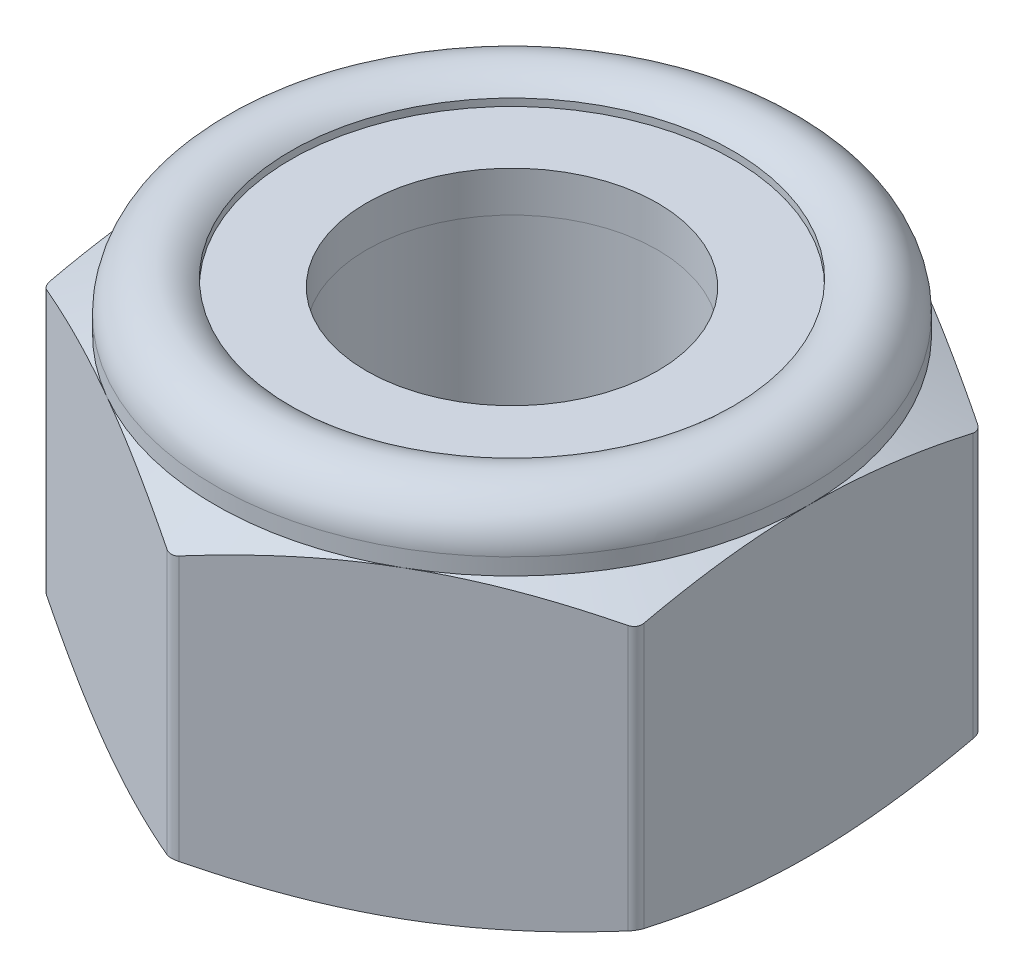
SolidWorks part; units mm, degrees
material "Alloy Steel"
ref_plane "Front Plane" through (0, 0, 0) normal (0, 0, 1) x (1, 0, 0)
ref_plane "Top Plane" through (0, 0, 0) normal (0, 1, 0) x (1, 0, 0)
ref_plane "Right Plane" through (0, 0, 0) normal (1, 0, 0) x (0, 0, -1)
sketch "Sketch1" plane through (0, 0, 0) normal (0, 0, 1) x (1, 0, 0)
  line L0 (0, -4) -> (0, 4) construction
  line L1 (6.5, 0) -> (-6.5, 0) construction
  line L2 (4, -4) -> (-4, -4) construction
  line L3 (4, -4) -> (4, -2.75) construction
  point P4 (0, 0)
  point P8 (0, 0)
  point P11 (0, -4)
  dimension "Height" = 8
  dimension "Width" = 13
  dimension "Thread Size" = 8
  dimension "Thread Pitch" = 1.25
sketch "Sketch2" plane through (0, 0, 0) normal (0, 1, 0) x (1, 0, 0)
  line L0 (-4, 0.5469) -> (-4, -0.5469) construction
  line L1 (0, 7.5056) -> (-6.5, 3.7528)
  line L2 (-6.5, 3.7528) -> (-6.5, -3.7528)
  line L3 (-6.5, -3.7528) -> (0, -7.5056)
  line L4 (0, -7.5056) -> (6.5, -3.7528)
  line L5 (6.5, -3.7528) -> (6.5, 3.7528)
  line L6 (6.5, 3.7528) -> (0, 7.5056)
  line L7 (-4, -0.5469) -> (-3.1881, -0.0781) construction
  line L8 (-3.1881, -0.0781) -> (-3.1881, 0.0781) construction
  line L9 (-3.1881, 0.0781) -> (-4, 0.5469) construction
  line L10 (-3.1881, 0) -> (-4, 0) construction
  line L11 (-3.5941, 0.3125) -> (-3.5941, -0.3125) construction
  line L12 (4, 0) -> (-4, 0) construction
  line L13 (6.5, 0) -> (-6.5, 0) construction
  circle A0 centre (0, 0) radius 6.5 construction
  circle A1 centre (0, 0) radius 3.1881
  point P19 (0, -3.1881)
  dimension "D1" = 0.1562
  dimension "D2" = 0.625
  dimension "D3" = 60
extrude "Boss-Extrude1" add sketch "Sketch2" along normal up to vertex (4 mm away) and the other way up to vertex (4 mm away) up to point (0, 4, 0) other way up to point (0, -4, 0)
fillet "Fillet1" radius 0.26 6 edges at (-6.5, 0, -3.7528) (0, 0, -7.5056) (-6.5, 0, 3.7528) (6.5, 0, -3.7528) (6.5, 0, 3.7528) (0, 0, 7.5056)
sketch "Sketch3" plane through (0, 0, 0) normal (1, 0, 0) x (0, 0, -1)
  line L0 (7.5056, 2.6667) -> (7.5056, 5)
  line L2 (6.5, -4) -> (7.5056, -3.5311)
  line L3 (3.8278, -4) -> (7.4305, -4) construction
  line L4 (7.5056, 4) -> (7.5056, -4) construction
  line L5 (7.5056, -3.5311) -> (7.5056, -4)
  line L6 (7.5056, -4) -> (6.5, -4)
  line L7 (6.5, 2.6667) -> (7.5056, 2.1978)
  line L8 (7.5056, 2.1978) -> (7.5056, 2.6667)
  line L11 (6.5, 2.6667) -> (6.5, 3.03)
  line L12 (3.8278, 4) -> (7.4305, 4) construction
  line L13 (3.1881, 2.6667) -> (4.8441, 2.6667)
  line L14 (4.8441, 2.6667) -> (4.8441, 3.7159)
  line L15 (4.8441, 2.6667) -> (6.5, 2.6667) construction
  line L16 (4.8441, 3.7159) -> (5.53, 3.03) construction
  line L17 (5.53, 3.03) -> (5.53, 4) construction
  line L18 (3.1881, 2.6667) -> (3.1881, 5)
  line L19 (3.1881, 5) -> (7.5056, 5)
  line L21 (3.1881, -4) -> (3.1881, -3.2)
  line L22 (-3.6027, -4) -> (3.6027, -4) construction
  line L24 (3.9881, -4) -> (3.1881, -4)
  line L25 (3.1881, -3.2) -> (3.9881, -4)
  arc A0 (6.5, 3.03) -> (4.8441, 3.7159) centre (5.53, 3.03) ccw
  point P0 (6.5, 2.6667)
  point P1 (6.5, 0)
  point P14 (3.1881, 0)
  dimension "D1" = 6.6667
  dimension "D2" = 25
  dimension "D3" = 45
  dimension "D4" = 1
  dimension "D5" = 0.8
revolve "Cut-Revolve2" cut sketch "Sketch3" angle 360 about L0
sketch "Sketch4" plane through (0, 0, 0) normal (1, 0, 0) x (0, 0, -1)
  line L0 (-4.8441, 3.7159) -> (-4.8441, 2.6667) construction
  line L1 (-3.1881, 2.6667) -> (-4.8441, 2.6667)
  line L2 (-3.1881, 2.6667) -> (-3.1881, 3.5559)
  line L3 (-3.1881, 3.5559) -> (-4.8441, 3.5559)
  line L4 (-4.8441, 2.6667) -> (-4.8441, 3.5559)
  line L5 (4.8441, 3.7159) -> (-4.8441, 3.7159) construction
  line L6 (3.1881, 2.6667) -> (-3.1881, 2.6667) construction
  dimension "D1" = 0.16
revolve "Revolve1" add sketch "Sketch4" angle 360 about L0
sketch "Sketch5" plane through (0, 0, 0) normal (0, 1, 0) x (1, 0, 0)
  circle A0 centre (0, 0) radius 3.1881 construction
  point P0 (0, -3.1881)
sketch "Sketch6" [suppressed] plane through (0, 0, 0) normal (0, 0, 1) x (1, 0, 0)
  line L0 (4, 2.6667) -> (4, -4)
  line L2 (0, -4) -> (6.5, -4) construction
  line L3 (4, -4) -> (0, -4)
  line L4 (0, -4) -> (0, 2.6667)
  line L5 (0, -4) -> (0, 4) construction
  line L6 (0, 2.6667) -> (4, 2.6667)
  line L7 (6.5, 2.6667) -> (3.25, 2.6667) construction
revolve "Revolve2" [suppressed] add sketch "Sketch6" angle 360 about L4
sketch "Sketch7" [suppressed] plane through (0, -4, 0) normal (0, -1, 0) x (1, 0, 0)
  circle A2 centre (0, 0) radius 4
  circle A3 centre (0, 0) radius 4
  dimension "D1" = 0
curve "Helix/Spiral1" [suppressed] pitch 1.25 height 8 turns 6.4
sketch "Sketch8" [suppressed] plane through (0, 0, 0) normal (0, 0, 1) x (1, 0, 0)
  line L0 (4.1353, -3.9219) -> (3.0528, -4.5469) construction
  line L1 (3.0528, -4.5469) -> (4.1353, -5.1719) construction
  line L2 (4.1353, -5.1719) -> (4.1353, -3.9219) construction
  line L3 (3.1881, -4.4687) -> (3.1881, -4.625)
  line L4 (4, -4) -> (4, -5.0937) construction
  line L5 (4, -4.5469) -> (4.1353, -4.5469) construction
  line L6 (3.0528, -4.5469) -> (3.1881, -4.5469) construction
  line L7 (4.0677, -4.5469) -> (4.0677, -5.1328) construction
  line L8 (3.1881, -4.4687) -> (4.1353, -3.9219)
  line L9 (4.1353, -3.9219) -> (4.0677, -5.1328)
  line L10 (3.1881, -4.625) -> (4.0677, -5.1328)
  dimension "D1" = 1.25
  dimension "D2" = 0.1562
sweep "Cut-Sweep1" [suppressed] cut profiles "Sketch8" path "Helix/Spiral1"
sketch "Sketch9" [suppressed] plane through (0, 0, 0) normal (0, 0, 1) x (1, 0, 0)
  line L0 (0, 0) -> (0, -4)
  line L1 (0, 0) -> (0, 0.8)
  line L2 (0, -4) -> (4, -4)
  line L3 (4, -4) -> (4.8, -4)
  line L4 (4.8, -4) -> (0, 0.8)
  dimension "D1" = 0.8
revolve "Revolve3" [suppressed] add sketch "Sketch9" angle 360 about L0
sketch "Sketch10" [suppressed] plane through (0, -4, 0) normal (0, -1, 0) x (1, 0, 0)
  circle A0 centre (0, 0) radius 3.9881 construction
  circle A1 centre (0, 0) radius 3.9881
extrude "Boss-Extrude2" [suppressed] add sketch "Sketch10" against normal up to surface (6.6667 mm away)
combine bodies "Combine1" [suppressed] operation type subtract main body 110 bodies to subtract 109
equation "\"D1@Sketch3\"=\"Height@sketch1\"*(5/6)"
equation "\"D5@Sketch3\"=\"Thread Size@Sketch1\"*.1"
equation "\"D4@Helix/Spiral1\"=\"Thread Pitch@sketch1\""
equation "\"D3@Helix/Spiral1\"=\"Height@sketch1\""
equation "\"D1@Sketch8\"=\"Thread Pitch@sketch1\""
equation "\"D2@Sketch8\"=\"Thread Pitch@sketch1\"/8"
equation "\"D1@Sketch9\"=\"Thread Size@Sketch1\" * .1"
equation "\"D1@Sketch2\"=\"Thread Pitch@sketch1\"/8"
equation "\"D2@Sketch2\"=\"Thread Pitch@sketch1\"/2"
equation "\"D1@Sketch4\" = \"Height@Sketch1\" * .02"
equation "\"D1@Fillet1\"=\"Width@sketch1\"*.02"
